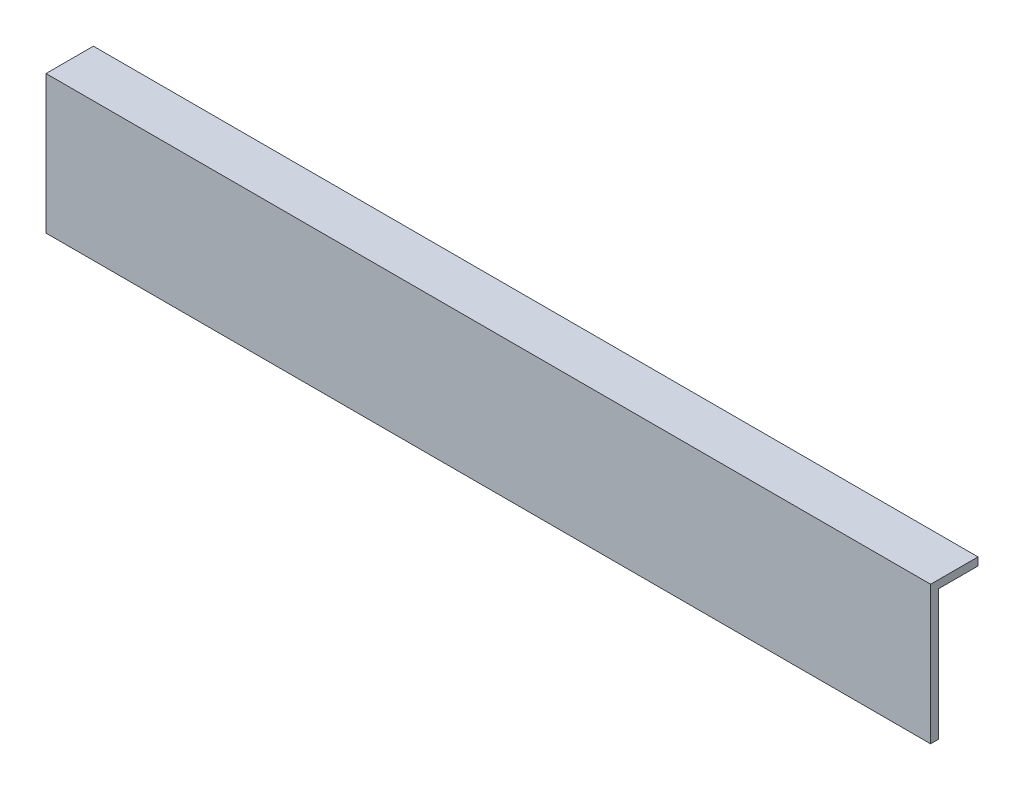
SolidWorks part; units mm, degrees
material "6061-T6 (SS)"
ref_plane "Front" through (0, 0, 0) normal (0, 0, 1) x (1, 0, 0)
ref_plane "Top" through (0, 0, 0) normal (0, 1, 0) x (1, 0, 0)
ref_plane "Right" through (0, 0, 0) normal (1, 0, 0) x (0, 0, -1)
sketch "Sketch1" plane through (0, 0, 0) normal (0, 0, 1) x (1, 0, 0)
  line L0 (-224, 0) -> (224, 0)
  line L1 (224, 0) -> (224, 70)
  line L2 (224, 70) -> (-224, 70)
  line L3 (-224, 70) -> (-224, 0)
  point P4 (0, 0)
  dimension "D1" = 448
  dimension "D2" = 70
base flange "Base-Flange1" sketch "Sketch1" thickness 4 reverse thickness direction no parameters "D1"=1
sketch "Sketch6" plane through (0, 0, -4) normal (0, 0, -1) x (-1, 0, 0)
  line L0 (-224, 0) -> (-224, 70) construction
  line L1 (224, 70) -> (-224, 70)
  line L2 (224, 70) -> (224, 66)
  line L3 (224, 66) -> (-224, 66)
  line L4 (-224, 70) -> (-224, 66)
  dimension "D1" = 4
extrude "Boss-Extrude1" add sketch "Sketch6" along normal blind 20
sketch "Bend-Lines1" [suppressed] plane through (0, 0, 0) normal (0, 1, 0) x (1, 0, 0)
sketch "Bounding-Box1" [suppressed] plane through (0, 0, 0) normal (0, 1, 0) x (1, 0, 0)
sheet metal parameters "Sheet-Metal1" thickness 4 parameters "D1"=1
flat pattern "Flat-Pattern1" [suppressed]
sketch "Bend-Lines2" plane through (0, 0, 0) normal (0, 1, 0) x (1, 0, 0)
sketch3d "Bounding-Box2" [suppressed]
  line L0 (-224, 0, 0) -> (224, 0, 0) construction
  line L1 (-224, 70, 0) -> (224, 70, 0) construction
  line L2 (-224, 0, 0) -> (-224, 70, 0) construction
  line L3 (224, 0, 0) -> (224, 70, 0) construction
sheet metal parameters "Sheet-Metal6" thickness 4 parameters "D1"=1
flat pattern "Flat-Pattern1"
sketch "Bend-Lines2" plane through (0, 0, 0) normal (0, 1, 0) x (1, 0, 0)
sketch3d "Bounding-Box2" [suppressed]
  line L0 (-224, 0, 0) -> (224, 0, 0) construction
  line L1 (-224, 70, 0) -> (224, 70, 0) construction
  line L2 (-224, 0, 0) -> (-224, 70, 0) construction
  line L3 (224, 0, 0) -> (224, 70, 0) construction
